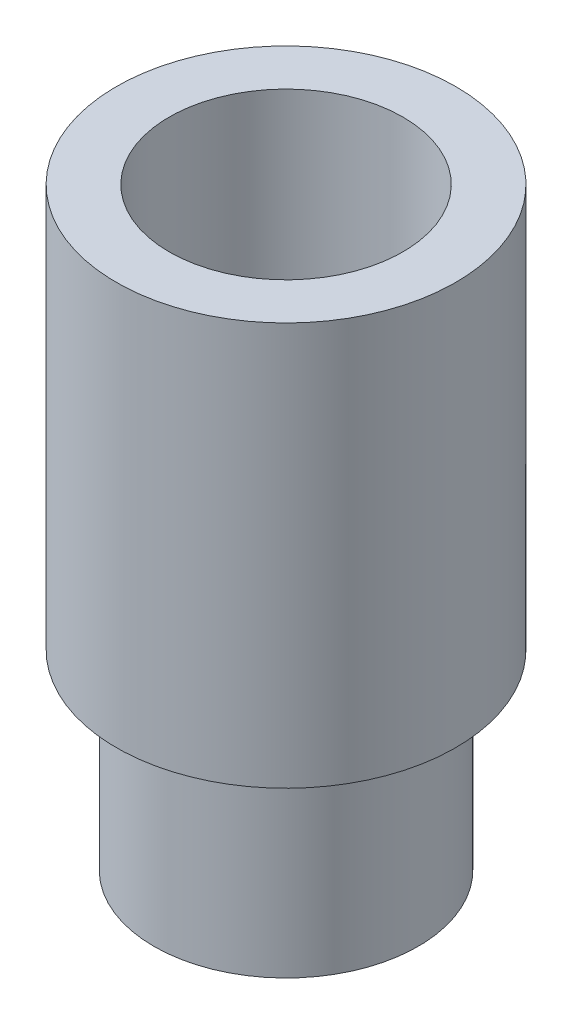
SolidWorks part; units mm, degrees
material "AISI 304"
ref_plane "Front Plane" through (0, 0, 0) normal (0, 0, 1) x (1, 0, 0)
ref_plane "Top Plane" through (0, 0, 0) normal (0, 1, 0) x (1, 0, 0)
ref_plane "Right Plane" through (0, 0, 0) normal (1, 0, 0) x (0, 0, -1)
sketch "Sketch1" plane through (0, 0, 0) normal (0, 0, 1) x (1, 0, 0)
  line L0 (0, 0) -> (0, 71.12) construction
  line L2 (13.9954, 0) -> (15.8242, 0)
  line L3 (13.9954, 0) -> (13.9954, 22.86)
  line L4 (13.9954, 22.86) -> (15.8242, 22.86)
  line L5 (15.8242, 0) -> (15.8242, 22.86)
  line L6 (13.9954, 22.86) -> (20.32, 22.86)
  line L7 (13.9954, 22.86) -> (13.9954, 71.12)
  line L8 (13.9954, 71.12) -> (20.32, 71.12)
  line L9 (20.32, 22.86) -> (20.32, 71.12)
  line L10 (13.9954, 32.86) -> (0, 32.86)
  line L11 (13.9954, 32.86) -> (13.9954, 22.86)
  line L12 (13.9954, 22.86) -> (0, 22.86)
  line L13 (0, 32.86) -> (0, 22.86)
  point P12 (0, 16.51)
  dimension "D1" = 48.26
  dimension "D2" = 31.6484
  dimension "D3" = 1.8288
  dimension "D4" = 22.86
  dimension "D5" = 40.64
  dimension "D6" = 10
  dimension "D7" = 6.35
revolve "Revolve1" add sketch "Sketch1" angle 360 about L0 region at (14.9098, 11.43, 0) region at (17.1577, 46.99, 0) region at (6.9977, 27.86, 0)
